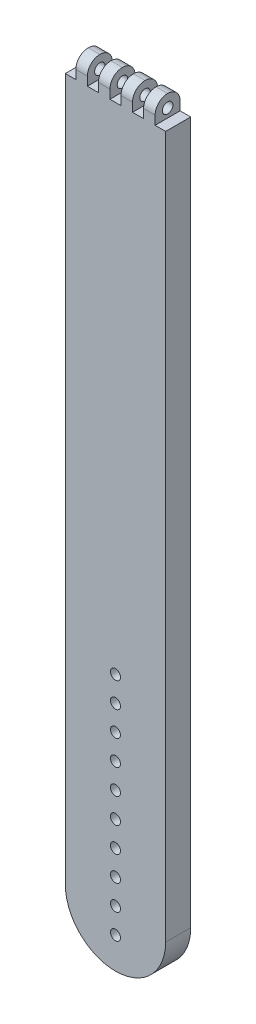
SolidWorks part; units mm, degrees
ref_plane "Front Plane" through (0, 0, 0) normal (0, 0, 1) x (1, 0, 0)
ref_plane "Top Plane" through (0, 0, 0) normal (0, 1, 0) x (1, 0, 0)
ref_plane "Right Plane" through (0, 0, 0) normal (1, 0, 0) x (0, 0, -1)
sketch "Sketch1" plane through (0, 0, 0) normal (0, 1, 0) x (1, 0, 0)
  line L1 (-20, 5) -> (20, 5)
  line L2 (-20, 5) -> (-20, -5)
  line L3 (-20, -5) -> (20, -5)
  line L4 (20, 5) -> (20, -5)
  line L5 (-20, 5) -> (20, -5) construction
  line L6 (-20, -5) -> (20, 5) construction
  point P0 (0, 0)
extrude "Boss-Extrude1" add sketch "Sketch1" along normal blind 300
fillet "Fillet1" radius 20 2 edges at (-20, 0, 0) (20, 0, 0)
sketch "Sketch2" plane through (0, 0, 5) normal (0, 0, 1) x (1, 0, 0)
  circle A0 centre (0, 12.5) radius 2
  dimension "D1" = 12.5
extrude "Cut-Extrude1" cut sketch "Sketch2" against normal through all
pattern_linear "LPattern1" count 10 spacing 10 along (0, 1, 0) of "Cut-Extrude1"
sketch "Sketch3" plane through (0, 300, 0) normal (0, 1, 0) x (1, 0, 0)
  line L0 (20, 5) -> (-20, 5) construction
  line L1 (15.8, 5) -> (11.2, 5)
  line L2 (15.8, 5) -> (15.8, -5)
  line L3 (15.8, -5) -> (11.2, -5)
  line L4 (11.2, 5) -> (11.2, -5)
  line L5 (13.5, -5) -> (13.5, 5) construction
  line L6 (15.8, 0) -> (11.2, 0) construction
  line L7 (-20, -5) -> (20, -5) construction
  line L8 (20, -5) -> (20, 5) construction
  point P276 (13.5, 0)
  dimension "D1" = 4.2
  dimension "D2" = 4.6
extrude "Boss-Extrude2" add sketch "Sketch3" along normal blind 8.5 contours L4 L3 L2 L1
fillet "Fillet2" radius 5 2 edges at (13.5, 308.5, 5) (13.5, 308.5, -5)
pattern_linear "LPattern2" count 4 spacing 9 along (-1, 0, 0) of "Fillet2", "Boss-Extrude2"
sketch "Sketch4" plane through (15.8, 0, 0) normal (1, 0, 0) x (0, 0, -1)
  circle A0 centre (0, 303.5) radius 2.1
extrude "Cut-Extrude2" cut sketch "Sketch4" against normal through all both and the other way through all
